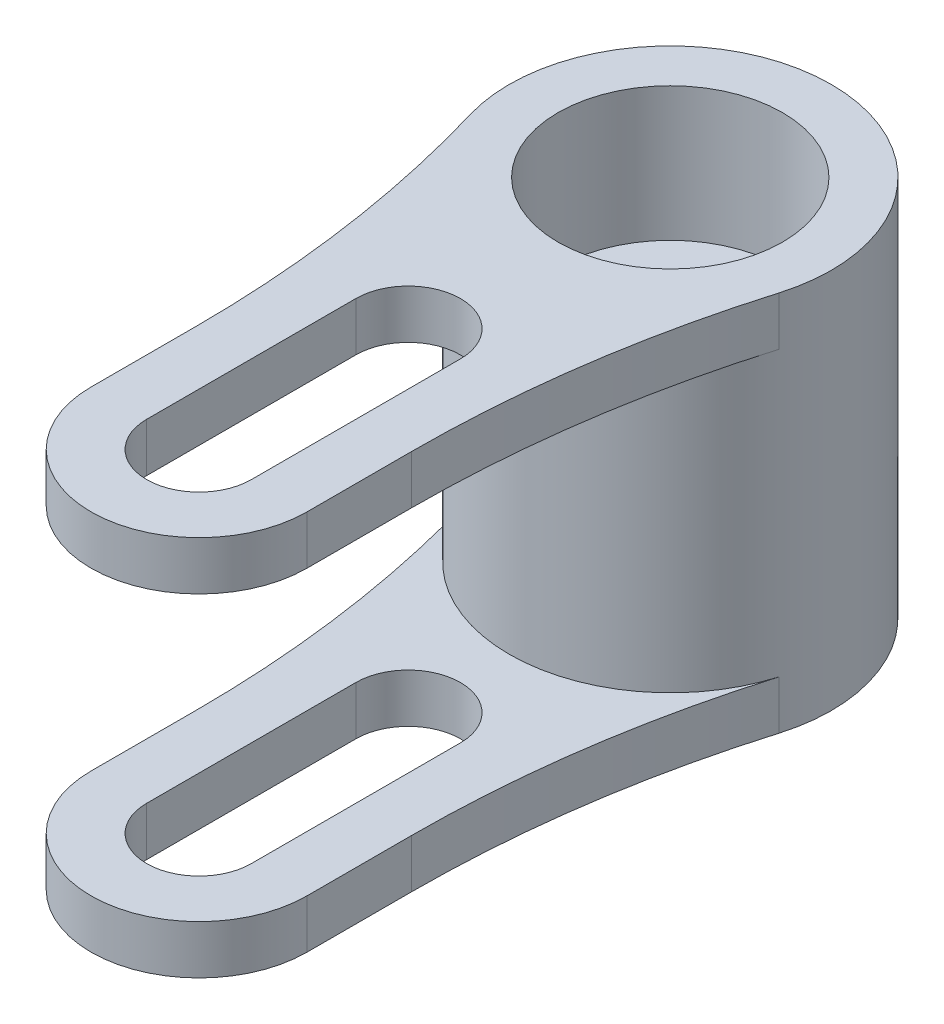
SolidWorks part; units mm, degrees
ref_plane "Front Plane" through (0, 0, 0) normal (0, 0, 1) x (1, 0, 0)
ref_plane "Top Plane" through (0, 0, 0) normal (0, 1, 0) x (1, 0, 0)
ref_plane "Right Plane" through (0, 0, 0) normal (1, 0, 0) x (0, 0, -1)
sketch "Sketch1" plane through (0, 0, 0) normal (0, 1, 0) x (1, 0, 0)
  line L0 (0, 5.775) -> (0, 4.025) construction
  line L1 (0, -9.4) -> (0, -16.9) construction
  line L2 (-3.875, -13.15) -> (-3.875, -16.9)
  line L3 (3.875, -16.9) -> (3.875, -13.15)
  line L4 (1.875, -9.4) -> (1.875, -16.9)
  line L5 (-1.875, -9.4) -> (-1.875, -16.9)
  line L6 (0, -7.525) -> (0, -5.775) construction
  line L7 (-3.875, -13.15) -> (3.875, -13.15) construction
  circle A0 centre (0, 0) radius 4.025
  circle A1 centre (0, 0) radius 5.775
  arc A2 (1.875, -9.4) -> (-1.875, -9.4) centre (0, -9.4) ccw
  arc A3 (-5.5388, -1.6347) -> (-3.875, -13.15) centre (-44.5559, -13.15) cw
  arc A4 (-3.875, -16.9) -> (3.875, -16.9) centre (0, -16.9) ccw
  arc A5 (3.875, -13.15) -> (5.5388, -1.6347) centre (44.5559, -13.15) cw
  arc A6 (-1.875, -16.9) -> (1.875, -16.9) centre (0, -16.9) ccw
  point P6 (0, -13.15)
  dimension "D1" = 8.05
  dimension "D2" = 1.75
  dimension "D3" = 3.75
  dimension "D4" = 2
  dimension "D5" = 7.5
  dimension "D6" = 1.75
extrude "Boss-Extrude1" add sketch "Sketch1" along normal mid plane 13.675 contours L3 A5 A1 A3 L2 A4 A6 L5 A2 L4 | A0 | A1 A0 region at (-4.0742, 0, 7.3009) region at (-0.8025, 0, -5.554) region at (0, 0, 0)
ref_plane "Plane1" through (0, -5.0875, 0) normal (0, -1, 0) x (-1, 0, 0)
ref_plane "Plane2" through (0, 5.0875, 0) normal (0, 1, 0) x (1, 0, 0)
extrude "Cut-Extrude1" cut sketch "Sketch1<4>" along normal up to surface (10.175 mm away) from surface contours L3 A5 A1 A3 L2 A4 A6 L5 A2 L4 region at (-4.0742, 0, 7.3009) up to plane "Plane2" starting at plane "Plane1"
sketch "Sketch1<4>" plane through (0, 0, 0) normal (0, 1, 0) x (1, 0, 0) same geometry as "Sketch1"
extrude "Cut-Extrude2" cut sketch "Sketch1<5>" against normal blind 4.8 from surface contours A0 region at (0, 0, 0) starting at face at (0, 6.8375, 13.15)
sketch "Sketch1<5>" plane through (0, 0, 0) normal (0, 1, 0) x (1, 0, 0) same geometry as "Sketch1"
equation "\"D1@Boss-Extrude1\"=9.525mm+1.75mm+1.75mm+.65mm"
